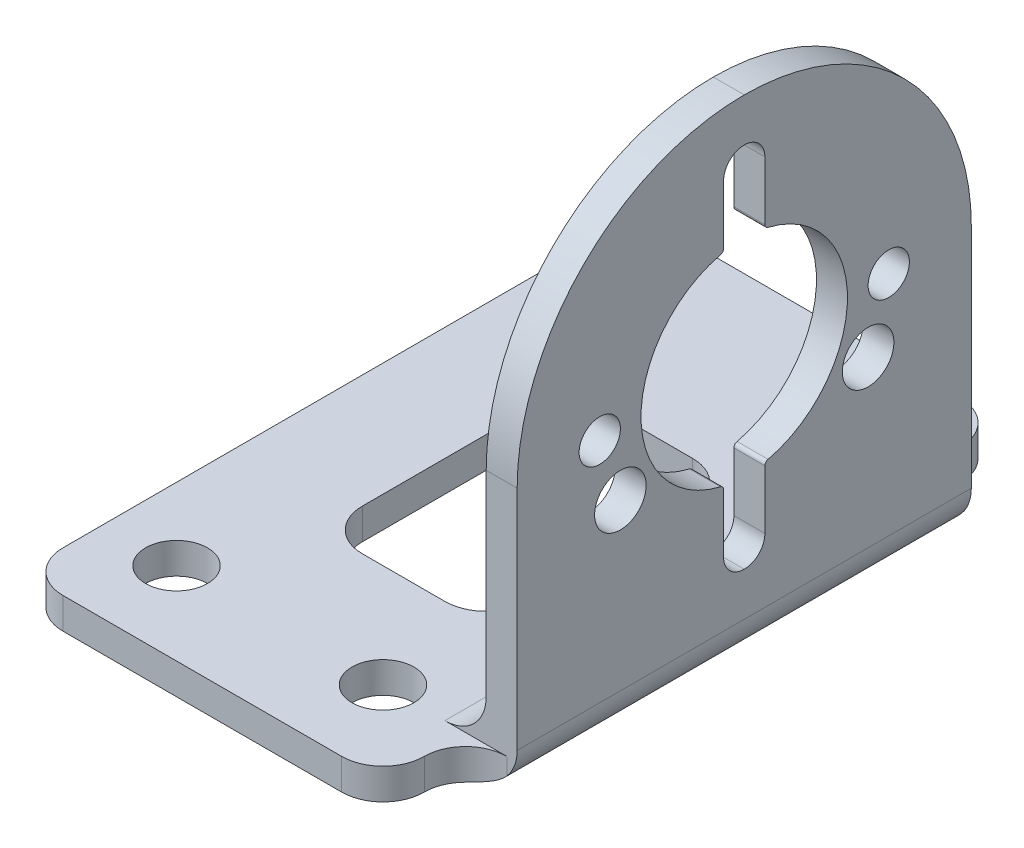
SolidWorks part; units mm, degrees
ref_plane "前视基准面" through (0, 0, 0) normal (0, 0, 1) x (1, 0, 0)
ref_plane "上视基准面" through (0, 0, 0) normal (0, 1, 0) x (1, 0, 0)
ref_plane "右视基准面" through (0, 0, 0) normal (1, 0, 0) x (0, 0, -1)
sketch "草图1" plane through (0, 0, 0) normal (0, 0, 1) x (1, 0, 0)
  line L1 (0, 0) -> (18.5, 0)
  line L2 (0, 0) -> (0, 1.5)
  line L3 (0, 1.5) -> (18.5, 1.5)
  line L5 (18.5, 0) -> (20, 0)
  line L6 (18.5, 1.5) -> (18.5, 24)
  line L7 (18.5, 24) -> (20, 24)
  line L8 (20, 0) -> (20, 24)
  dimension "D1" = 1.5
  dimension "D2" = 1.5
  dimension "D3" = 1.5
  dimension "D4" = 24
  dimension "D5" = 20
extrude "凸台-拉伸1" add sketch "草图1" along normal blind 30
sketch "草图2" plane through (0, 1.5, 0) normal (0, 1, 0) x (1, 0, 0)
  line L0 (0, -15) -> (23.5649, -15) construction
  line L1 (17.5, 1.6594) -> (22.3275, 1.6594)
  line L2 (17.5, 1.6594) -> (17.5, -4)
  line L3 (17.5, -4) -> (22.3275, -4)
  line L4 (22.3275, 1.6594) -> (22.3275, -4)
  line L5 (0, -30) -> (0, 0) construction
  line L6 (18.5, -30) -> (18.5, 0) construction
  line L7 (18.5, 0) -> (0, 0) construction
  line L8 (22.3275, -31.6594) -> (22.3275, -26)
  line L9 (17.5, -26) -> (22.3275, -26)
  line L10 (17.5, -31.6594) -> (17.5, -26)
  line L11 (17.5, -31.6594) -> (22.3275, -31.6594)
  dimension "D1" = 1
  dimension "D2" = 4
extrude "切除-拉伸1" cut sketch "草图2" against normal blind 30 and the other way blind 30
fillet "圆角1" radius 11 2 edges at (19.25, 24, 26) (19.25, 24, 4)
sketch "草图3" plane through (0, 1.5, 0) normal (0, 1, 0) x (1, 0, 0)
  line L0 (0, -15) -> (21.8354, -15) construction
  line L1 (0, -30) -> (0, 0) construction
  line L2 (20, -15) -> (20, -4) construction
  line L3 (18.5, -26) -> (18.5, -4) construction
  line L4 (7.5, -9) -> (11.5, -9)
  line L5 (5.5, -11) -> (5.5, -19)
  line L6 (7.5, -21) -> (11.5, -21)
  line L7 (13.5, -11) -> (13.5, -19)
  circle A0 centre (13.5, -4) radius 1.5
  circle A1 centre (3.5, -4) radius 1.5
  circle A2 centre (3.5, -26) radius 1.5
  circle A3 centre (13.5, -26) radius 1.5
  arc A4 (11.5, -21) -> (13.5, -19) centre (11.5, -19) ccw
  arc A5 (5.5, -19) -> (7.5, -21) centre (7.5, -19) ccw
  arc A6 (11.5, -9) -> (13.5, -11) centre (11.5, -11) cw
  arc A7 (7.5, -9) -> (5.5, -11) centre (7.5, -11) ccw
  point P22 (13.5, -21)
  point P25 (5.5, -21)
  point P30 (5.5, -9)
  dimension "D1" = 3
  dimension "D2" = 3
  dimension "D10" = 2
  dimension "D3" = 10
  dimension "D4" = 6.5
  dimension "D5" = 11
  dimension "D6" = 8
  dimension "D7" = 12
  dimension "D8" = 6
  dimension "D9" = 5
extrude "切除-拉伸2" cut sketch "草图3" against normal blind 30
sketch "草图4" plane through (18.5, 0, 0) normal (-1, 0, 0) x (0, 0, 1)
  line L1 (7.7485, 13) -> (23.6417, 13) construction
  line L2 (15, 19.7587) -> (15, 5.8569) construction
  line L3 (16, 8.101) -> (16, 4.101)
  line L5 (14, 17.899) -> (14, 21.899)
  line L6 (14, 21.899) -> (16, 21.899)
  line L7 (16, 17.899) -> (16, 21.899)
  line L8 (14, 4.101) -> (16, 4.101)
  line L9 (14, 8.101) -> (14, 4.101)
  arc A0 (14, 17.899) -> (14, 8.101) centre (15, 13) ccw
  circle A1 centre (8, 13) radius 1
  circle A2 centre (22, 13) radius 1
  circle A3 centre (9, 10) radius 1.25
  circle A4 centre (21, 10) radius 1.25
  arc A5 (16, 8.101) -> (16, 17.899) centre (15, 13) ccw
  dimension "D1" = 10
  dimension "D2" = 2
  dimension "D4" = 2.5
  dimension "D3" = 7
  dimension "D5" = 6
  dimension "D6" = 3
  dimension "D7" = 1
  dimension "D8" = 4
  dimension "D9" = 4
extrude "切除-拉伸3" cut sketch "草图4" against normal through all
fillet "圆角2" radius 1 4 edges at (19.25, 4.101, 14) (19.25, 4.101, 16) (19.25, 21.899, 16) (19.25, 21.899, 14)
fillet "圆角3" radius 0.2 4 edges at (19.25, 8.101, 16) (19.25, 8.101, 14) (19.25, 17.899, 16) (19.25, 17.899, 14)
fillet "圆角4" radius 2 6 edges at (17.5, 0.75, 26) (17.5, 0.75, 4) (17.5, 0.75, 0) (17.5, 0.75, 30) (0, 0.75, 30) (0, 0.75, 0)
fillet "圆角5" radius 2 2 edges at (20, 0, 15) (18.5, 1.5, 15)
